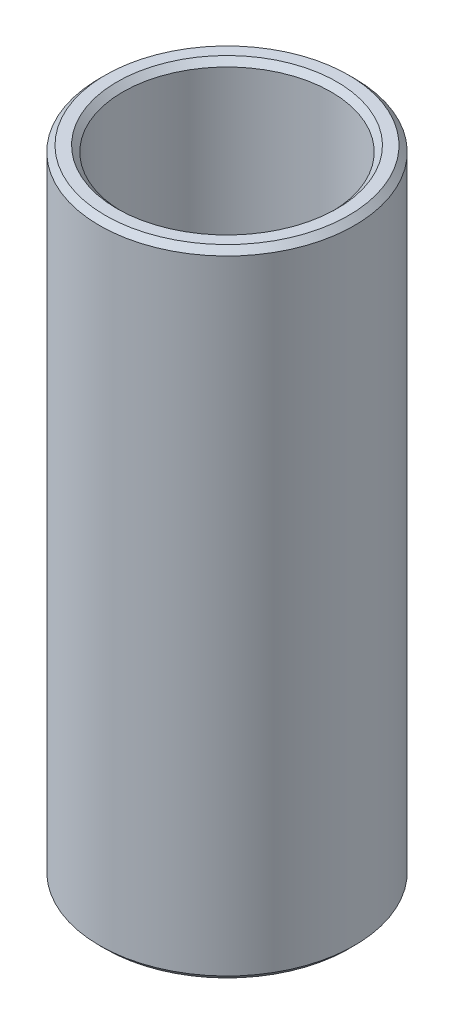
SolidWorks part; units mm, degrees
ref_plane "Front Plane" through (0, 0, 0) normal (0, 0, 1) x (1, 0, 0)
ref_plane "Top Plane" through (0, 0, 0) normal (0, 1, 0) x (1, 0, 0)
ref_plane "Right Plane" through (0, 0, 0) normal (1, 0, 0) x (0, 0, -1)
sketch "Sketch1" plane through (0, 0, 0) normal (0, 1, 0) x (1, 0, 0)
  circle A0 centre (0, 0) radius 30
  dimension "SLEEVE_OD" = 60
extrude "Boss-Extrude1" add sketch "Sketch1" along normal blind 149.4946
sketch "Sketch2" plane through (0, 0, 0) normal (0, 1, 0) x (1, 0, 0)
  circle A0 centre (0, 0) radius 24.5071
  dimension "BORE_D" = 49.0141
extrude "Cut-Extrude1" cut sketch "Sketch2" along normal through all
chamfer "Chamfer1" distance 1.3689 angle 45 4 edges at (0, 149.4946, 24.5071) (0, 0, 24.5071) (0, 0, 30) (0, 149.4946, 30)
